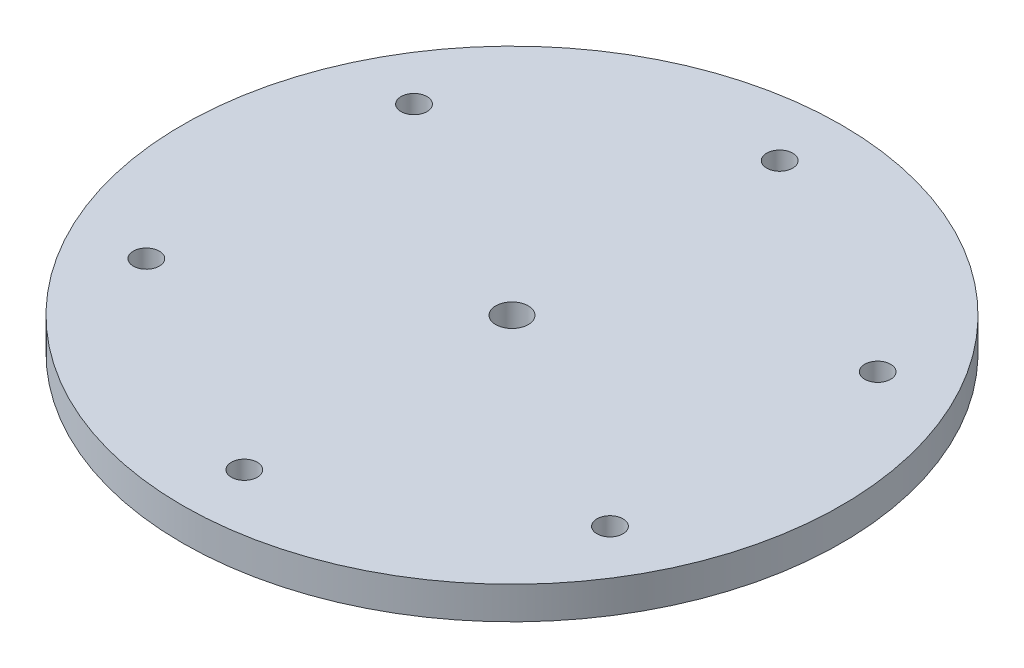
SolidWorks part; units mm, degrees
ref_plane "Front Plane" through (0, 0, 0) normal (0, 0, 1) x (1, 0, 0)
ref_plane "Top Plane" through (0, 0, 0) normal (0, 1, 0) x (1, 0, 0)
ref_plane "Right Plane" through (0, 0, 0) normal (1, 0, 0) x (0, 0, -1)
sketch "Sketch1" plane through (0, 0, 0) normal (0, 1, 0) x (1, 0, 0)
  circle A0 centre (0, 0) radius 76.2
  circle A1 centre (0, 0) radius 72.95
  dimension "D1" = 152.4
  dimension "D2" = 3.25
sketch "Sketch2" plane through (0, 0, 0) normal (0, 0, 1) x (1, 0, 0)
  line L0 (0, 0) -> (0, -1)
  line L1 (76.2, 0) -> (-76.2, 0) construction
  line L3 (0, -1) -> (-72.95, -1)
  line L4 (72.95, 0) -> (-72.95, 0) construction
  line L6 (-101.2, 9) -> (0, 9)
  line L7 (-72.95, 0) -> (-72.95, -1)
  line L8 (0, 9) -> (0, -1)
  line L22 (-76.2, 0) -> (-72.95, 0)
  line L26 (-76.2, 0) -> (-76.2, -1)
  line L27 (-76.2, -1) -> (-101.2, -1)
  line L28 (-101.2, -1) -> (-101.2, 9)
  point P4 (0, 0)
  point P5 (0, 0)
  dimension "D12" = 1
  dimension "D13" = 25
  dimension "D14" = 10
  dimension "D15" = 1
revolve "Revolve1" add sketch "Sketch2" angle 360 about L8
sketch "Sketch3" plane through (0, -1, 0) normal (0, -1, 0) x (1, 0, 0)
  line L0 (0, 0) -> (0, 76.2)
  line L1 (0, 76.2) -> (0, 101.2)
  circle A0 centre (0, 0) radius 76.2 construction
  circle A1 centre (0, 0) radius 101.2 construction
  circle A2 centre (0, 82.2) radius 4
  circle A3 centre (71.1873, 41.1) radius 4
  circle A4 centre (71.1873, -41.1) radius 4
  circle A5 centre (0, -82.2) radius 4
  circle A6 centre (-71.1873, -41.1) radius 4
  circle A7 centre (-71.1873, 41.1) radius 4
  point P23 (0, 0)
  dimension "D2" = 8
  dimension "D1" = 6
  dimension "D3" = 6
extrude "Cut-Extrude1" cut sketch "Sketch3" against normal blind 10 contours A7 | A6 | A4 | A3 | L1 A2 | L1 A2 | A5 region at (-1.6977, -1, 82.2) region at (1.6977, -1, 82.2) region at (71.1873, -1, 41.1) region at (71.1873, -1, -41.1) region at (-71.1873, -1, -41.1) region at (-71.1873, -1, 41.1)
sketch "Sketch4" plane through (0, 9, 0) normal (0, 1, 0) x (1, 0, 0)
  circle A0 centre (0, 0) radius 5
extrude "Cut-Extrude2" cut sketch "Sketch4" against normal blind 10
